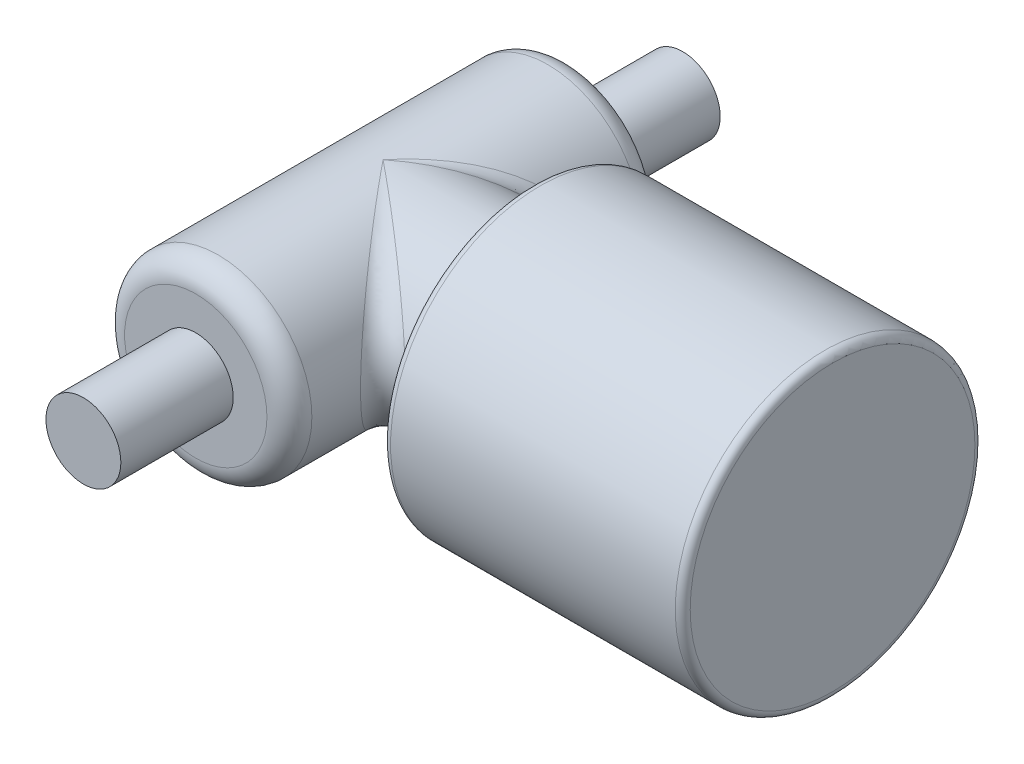
SolidWorks part; units mm, degrees
ref_plane "Front Plane" through (0, 0, 0) normal (0, 0, 1) x (1, 0, 0)
ref_plane "Top Plane" through (0, 0, 0) normal (0, 1, 0) x (1, 0, 0)
ref_plane "Right Plane" through (0, 0, 0) normal (1, 0, 0) x (0, 0, -1)
sketch "Sketch1" plane through (0, 0, 0) normal (1, 0, 0) x (0, 0, -1)
  circle A0 centre (0, 0) radius 20
  dimension "D1" = 40
extrude "Boss-Extrude1" add sketch "Sketch1" against normal blind 40 from offset 60
fillet "Fillet2" radius 1 2 edges at (60, 0, -20) (20, 0, -20)
sketch "Sketch2" plane through (0, 0, 0) normal (1, 0, 0) x (0, 0, -1)
  circle A0 centre (0, 0) radius 12.5
  dimension "D1" = 25
extrude "Boss-Extrude2" add sketch "Sketch2" along normal up to surface (20 mm away) up to face at (20, 0, -19)
sketch "Sketch3" plane through (0, 0, 0) normal (0, 0, 1) x (1, 0, 0)
  circle A0 centre (0, 0) radius 12.5
extrude "Boss-Extrude3" add sketch "Sketch3" along normal mid plane 50
fillet "Fillet4" radius 3 2 edges at (12.5, 0, 12.5) (12.5, 0, -12.5)
fillet "Fillet5" radius 3 2 edges at (12.5, 0, -25) (12.5, 0, 25)
sketch "Sketch4" plane through (0, 0, 0) normal (0, 0, 1) x (1, 0, 0)
  circle A0 centre (0, 0) radius 5
  dimension "D1" = 10
extrude "Boss-Extrude4" add sketch "Sketch4" along normal mid plane 80
